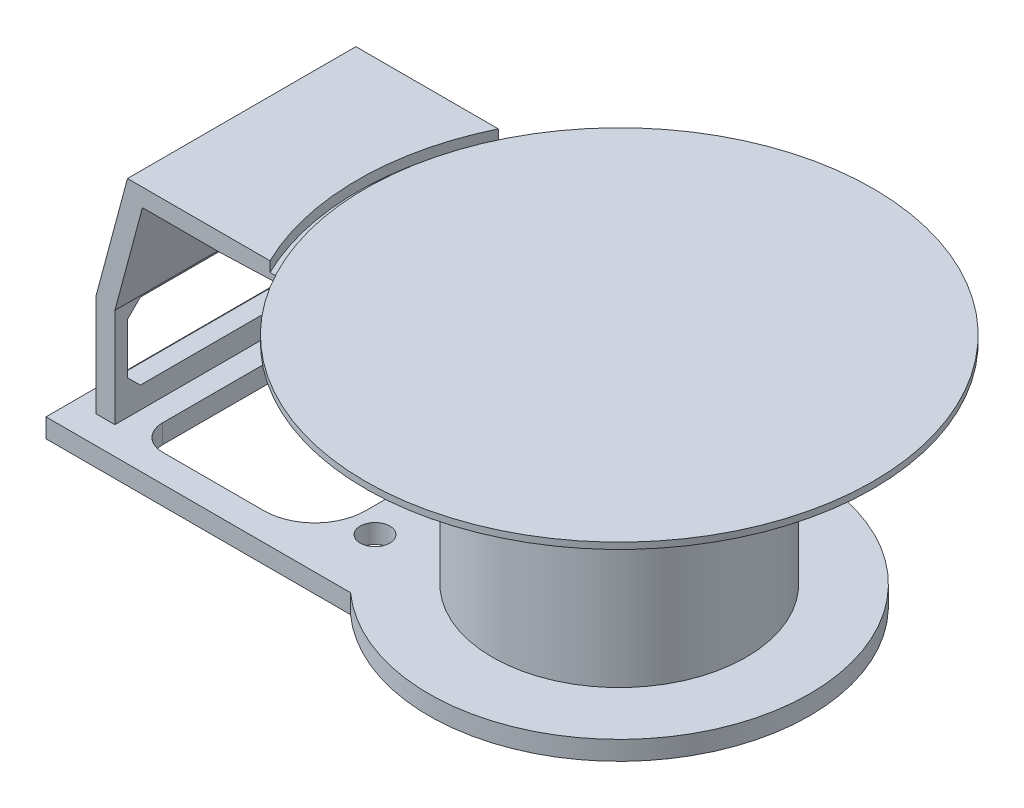
SolidWorks part; units mm, degrees
material "Ti-6Al-2Sn-2Zr-2Mo-2Cr-0.25Si (SS)"
ref_plane "Front Plane" through (0, 0, 0) normal (0, 0, 1) x (1, 0, 0)
ref_plane "Top Plane" through (0, 0, 0) normal (0, 1, 0) x (1, 0, 0)
ref_plane "Right Plane" through (0, 0, 0) normal (1, 0, 0) x (0, 0, -1)
sketch "Sketch1" plane through (0, 0, 0) normal (0, 1, 0) x (1, 0, 0)
  line L0 (0, 0) -> (-310.1158, 0) construction
  line L1 (-50, 55.9017) -> (-170, 55.9017)
  line L3 (-50, -55.9017) -> (-170, -55.9017)
  line L4 (-170, 55.9017) -> (-170, -55.9017)
  line L6 (-95, -45) -> (-135, -45)
  line L7 (-75, -25) -> (-75, 25)
  line L8 (-95, 45) -> (-135, 45)
  line L9 (-145, -35) -> (-145, 35)
  line L10 (-75, -45) -> (-145, 45) construction
  line L11 (-75, 45) -> (-145, -45) construction
  arc A0 (-50, -55.9017) -> (-50, 55.9017) centre (0, 0) ccw
  circle A1 centre (0, 0) radius 50
  arc A2 (-135, -45) -> (-145, -35) centre (-135, -35) cw
  arc A3 (-135, 45) -> (-145, 35) centre (-135, 35) ccw
  arc A4 (-75, -25) -> (-95, -45) centre (-95, -25) cw
  arc A5 (-75, 25) -> (-95, 45) centre (-95, 25) ccw
  point P8 (-110, 0)
  dimension "D1" = 150
  dimension "D2" = 100
  dimension "D6" = 10
  dimension "D7" = 20
  dimension "D3" = 111.8034
  dimension "D4" = 120
  dimension "D5" = 110
  dimension "D8" = 40
  dimension "D9" = 70
extrude "Boss-Extrude1" add sketch "Sketch1" along normal blind 7.5
extrude "Boss-Extrude2" add sketch "Sketch1<2>" along normal blind 90 contours A1 region at (0, 0, 0)
sketch "Sketch1<2>" plane through (0, 0, 0) normal (0, 1, 0) x (1, 0, 0) same geometry as "Sketch1"
sketch "Sketch2" plane through (0, 7.5, 0) normal (0, 1, 0) x (1, 0, 0)
  line L0 (0, 0) -> (-211.2043, 0) construction
  line L1 (-153.75, -45) -> (-161.25, -45)
  line L2 (-153.75, -45) -> (-153.75, 45)
  line L3 (-153.75, 45) -> (-161.25, 45)
  line L4 (-161.25, -45) -> (-161.25, 45)
  line L5 (-153.75, -45) -> (-161.25, 45) construction
  line L6 (-153.75, 45) -> (-161.25, -45) construction
  point P0 (-157.5, 0)
  dimension "D1" = 90
  dimension "D2" = 157.5
  dimension "D3" = 7.5
extrude "Boss-Extrude3" add sketch "Sketch2" along normal blind 40
sketch "Sketch4" plane through (0, 90, 0) normal (0, 1, 0) x (1, 0, 0)
  circle A0 centre (0, 0) radius 100
  dimension "D1" = 200
extrude "Boss-Extrude4" add sketch "Sketch4" along normal blind 2.5
ref_plane "Plane1" through (-162.3233, 43.4944, 0) normal (-0.9659, 0.2588, 0) x (0, 0, 1)
sketch "Sketch7" plane through (-162.3233, 43.4944, 0) normal (-0.9659, 0.2588, 0) x (0, 0, 1)
  line L1 (-45, 4.1469) -> (45, 4.1469)
  line L2 (-45, 4.1469) -> (-45, 54.1469)
  line L3 (-45, 54.1469) -> (45, 54.1469)
  line L4 (45, 4.1469) -> (45, 54.1469)
  dimension "D1" = 50
extrude "Boss-Extrude9" add sketch "Sketch7" against normal blind 7.5
sketch "Sketch3" plane through (-161.25, 0, 0) normal (-1, 0, 0) x (0, 0, 1)
  line L0 (35, 46) -> (40, 41)
  line L1 (-35, 46) -> (35, 46)
  line L2 (-40, 41) -> (-40, 21)
  line L3 (-35, 16) -> (35, 16)
  line L4 (40, 41) -> (40, 21)
  line L5 (-40, 41) -> (-35, 46)
  line L6 (-40, 21) -> (-35, 16)
  line L8 (-45, 7.5) -> (45, 7.5) construction
  line L9 (35, 16) -> (40, 21)
  line L11 (-45, 47.5) -> (-45, 7.5) construction
  point P0 (-40, 46)
  point P1 (40, 16)
  point P2 (-40, 16)
  point P3 (40, 46)
  point P6 (0, 16)
  dimension "D1" = 80
  dimension "D2" = 30
  dimension "D3" = 45
  dimension "D4" = 8.5
extrude "Cut-Extrude1" cut sketch "Sketch3" against normal up to next
sketch "Sketch14" plane through (0, 90, 0) normal (0, -1, 0) x (1, 0, 0)
  line L1 (-54.8413, 45) -> (-149.8413, 45)
  line L2 (-54.8413, 45) -> (-54.8413, -45)
  line L3 (-54.8413, -45) -> (-149.8413, -45)
  line L4 (-149.8413, 45) -> (-149.8413, -45)
  line L5 (-54.8413, 45) -> (-149.8413, -45) construction
  line L6 (-54.8413, -45) -> (-149.8413, 45) construction
  point P0 (-102.3413, 0)
  dimension "D1" = 95
extrude "Boss-Extrude13" add sketch "Sketch14" along normal blind 3
sketch "Sketch15" plane through (0, 90, 0) normal (0, 1, 0) x (1, 0, 0)
  line L0 (-142.0976, 45) -> (-89.3029, 45) construction
  line L1 (-89.3029, -45) -> (-142.0976, -45) construction
  line L2 (-92.6499, 45) -> (-144.6868, 45)
  line L3 (-141.0646, 45) -> (-148.309, 45) construction
  line L4 (-144.6868, 45) -> (-144.6868, -45)
  line L5 (-141.0646, -45) -> (-148.309, -45) construction
  line L6 (-144.6868, -45) -> (-92.6499, -45)
  arc A0 (-92.6499, 45) -> (-92.6499, -45) centre (0, 0) ccw
  dimension "D1" = 103
extrude "Boss-Extrude14" add sketch "Sketch15" along normal blind 5
sketch "Sketch17" plane through (0, 95, 0) normal (0, 1, 0) x (1, 0, 0)
  line L0 (-92.6499, 45) -> (-144.6868, 45) construction
  line L1 (-86.6011, 45) -> (-157.5, 45)
  line L2 (-86.6011, 45) -> (-86.6011, -45)
  line L3 (-86.6011, -45) -> (-157.5, -45)
  line L4 (-157.5, 45) -> (-157.5, -45)
  line L5 (-161.25, -45) -> (-153.75, -45) construction
extrude "Cut-Extrude3" cut sketch "Sketch17" against normal blind 1 and the other way blind 5
chamfer "Chamfer3" distance 2 angle 88 1 edges at (-54.8413, 87, 0) first distance on face at (-54.8413, 88.5, 0)
scale "Scale1" scale about centroid uniform scaling yes scale factor 0.3
sketch "Sketch19" plane through (0, 34.5083, 0) normal (0, 1, 0) x (1, 0, 0)
  line L0 (0, 0) -> (-61.991, 0) construction
  line L1 (-61.991, 16.7705) -> (-61.991, -16.7705) construction
  line L2 (-30.491, 9.375) -> (-30.491, -9.375) construction
  line L3 (-33.491, -7.5) -> (-33.491, 7.5) construction
  circle A0 centre (-30.491, 9.375) radius 1.75
  circle A1 centre (-30.491, -9.375) radius 1.75
  dimension "D1" = 3.5
  dimension "D2" = 3.5
  dimension "D3" = 18.75
  dimension "D4" = 3
extrude "Cut-Extrude4" cut sketch "Sketch19" against normal up to next
